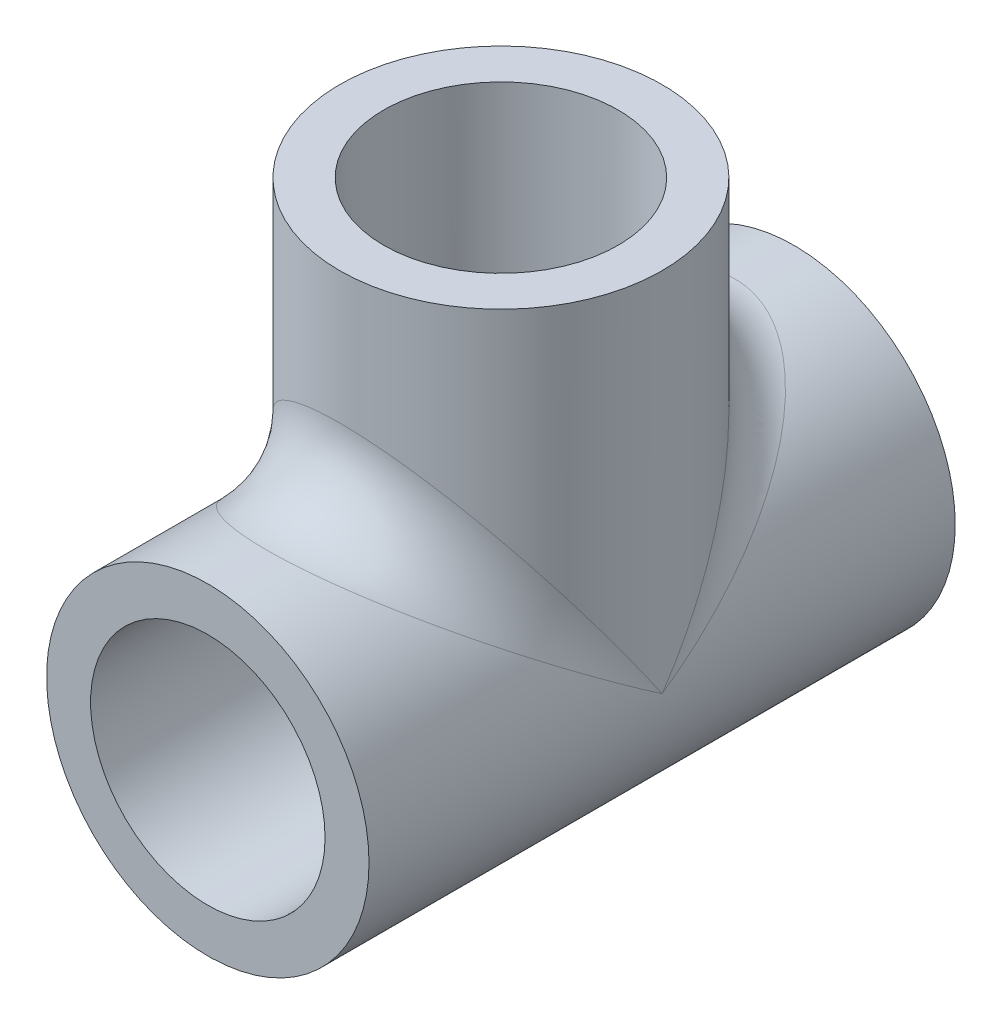
SolidWorks part; units mm, degrees
material "ABS"
ref_plane "Front Plane" through (0, 0, 0) normal (0, 0, 1) x (1, 0, 0)
ref_plane "Top Plane" through (0, 0, 0) normal (0, 1, 0) x (1, 0, 0)
ref_plane "Right Plane" through (0, 0, 0) normal (1, 0, 0) x (0, 0, -1)
sketch "Sketch1" plane through (0, 0, 0) normal (0, 0, 1) x (1, 0, 0)
  circle A0 centre (0, 0) radius 8
  circle A1 centre (0, 0) radius 11
  dimension "D1" = 16
  dimension "D2" = 22
extrude "Boss-Extrude1" add sketch "Sketch1" along normal mid plane 40
sketch "Sketch3" plane through (0, 0, 0) normal (0, 1, 0) x (1, 0, 0)
  circle A0 centre (0, 0) radius 8
  circle A1 centre (0, 0) radius 11
  dimension "D1" = 16
  dimension "D2" = 22
extrude "Boss-Extrude2" add sketch "Sketch3" against normal up to surface (14 mm away) from offset 25 up to face at (11, 0, 20)
fillet "Fillet1" radius 5 2 edges at (0, 11, -11) (0, 11, 11)
